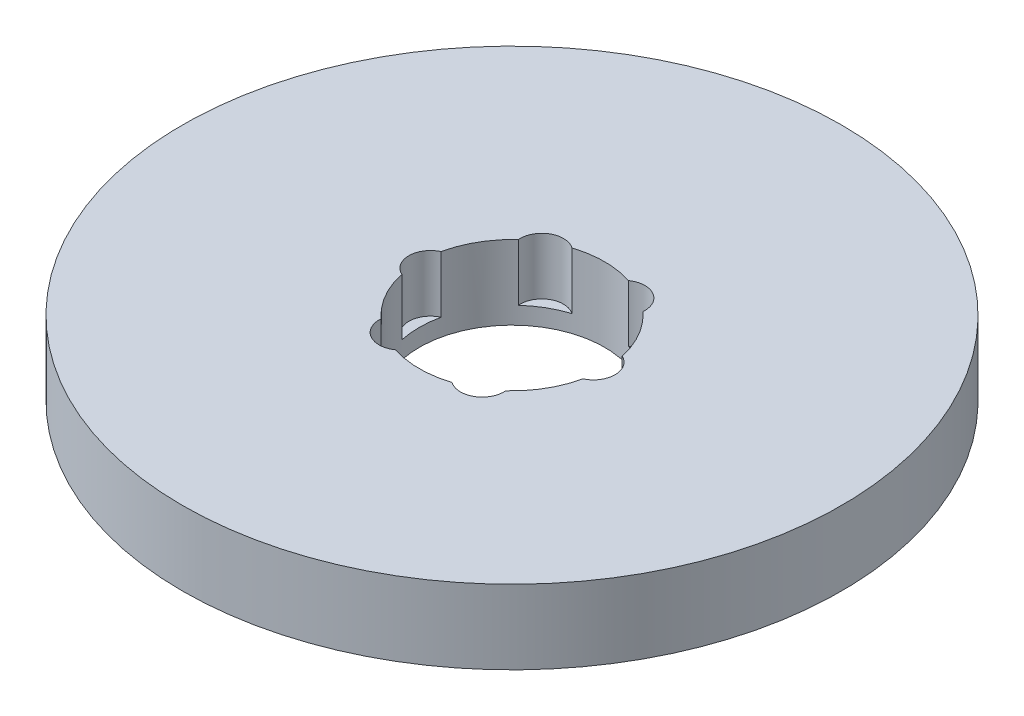
SolidWorks part; units mm, degrees
ref_plane "Front Plane" through (0, 0, 0) normal (0, 0, 1) x (1, 0, 0)
ref_plane "Top Plane" through (0, 0, 0) normal (0, 1, 0) x (1, 0, 0)
ref_plane "Right Plane" through (0, 0, 0) normal (1, 0, 0) x (0, 0, -1)
sketch "Sketch1" plane through (0, 0, 0) normal (0, 1, 0) x (1, 0, 0)
  circle A0 centre (0, 0) radius 80
  dimension "FLANGE_OD" = 160
extrude "Boss-Extrude1" add sketch "Sketch1" along normal blind 18
sketch "Sketch2" plane through (0, 0, 0) normal (0, 1, 0) x (1, 0, 0)
  circle A0 centre (0, 0) radius 22.5
  dimension "BORE_D" = 45
extrude "Cut-Extrude1" cut sketch "Sketch2" along normal through all
sketch "Sketch3" plane through (0, 18, 0) normal (0, 1, 0) x (1, 0, 0)
  circle A0 centre (0, 0) radius 19.7715 construction
  circle A1 centre (-19.7715, 0) radius 5.2586
  dimension "BOLT_D" = 10.5171
  dimension "BOLT_PCD" = 39.5431
extrude "Cut-Extrude2" cut sketch "Sketch3" against normal blind 13.8059
pattern_circular "CirPattern1" count 6 over 360 about axis through (0, 0, 0) along (0, 1, 0) of "Cut-Extrude2"
